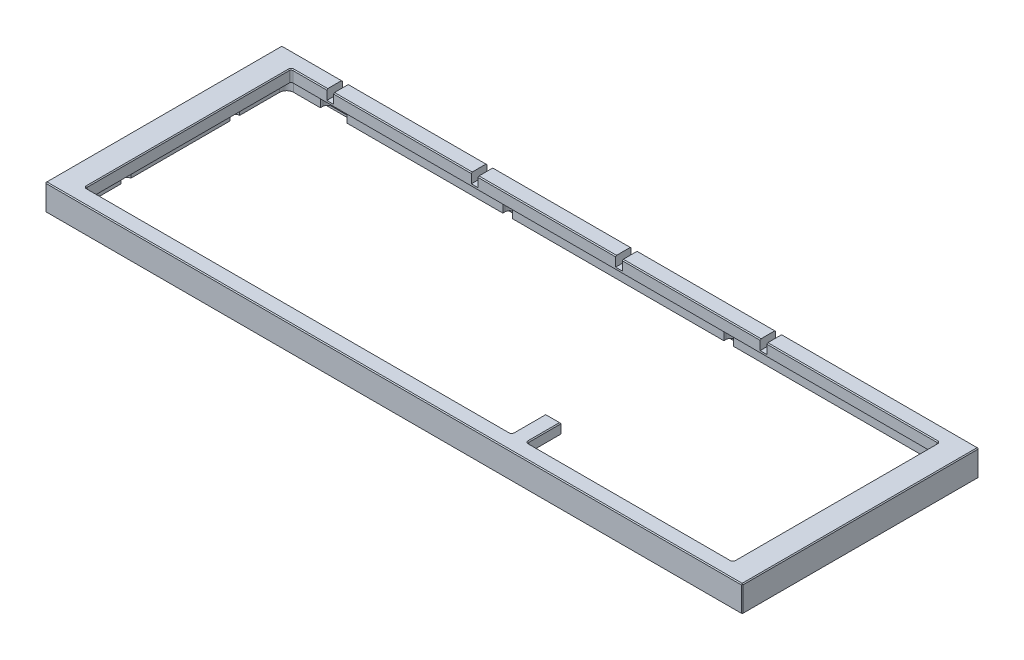
SolidWorks part; units mm, degrees
material "6061-T6 (SS)"
ref_plane "Front Plane" through (0, 0, 0) normal (0, 0, 1) x (1, 0, 0)
ref_plane "Top Plane" through (0, 0, 0) normal (0, 1, 0) x (1, 0, 0)
ref_plane "Right Plane" through (0, 0, 0) normal (1, 0, 0) x (0, 0, -1)
sketch "Sketch1" plane through (0, 0, 0) normal (0, 1, 0) x (1, 0, 0)
  line L1 (0, 0) -> (390.74, 0)
  line L2 (0, 0) -> (0, 132.7)
  line L3 (0, 132.7) -> (390.74, 132.7)
  line L4 (390.74, 0) -> (390.74, 132.7)
  line L5 (13.92, 124) -> (376.82, 124)
  line L6 (13.92, 124) -> (13.92, 8.7)
  line L7 (13.92, 8.7) -> (376.82, 8.7)
  line L8 (376.82, 124) -> (376.82, 8.7)
  point P9 (195.37, 124)
  point P10 (195.37, 132.7)
  point P11 (13.92, 66.35)
  point P12 (0, 66.35)
  dimension "D1" = 362.9
  dimension "D2" = 115.3
  dimension "D3" = 8.7
  dimension "D4" = 13.92
extrude "Main Body" add sketch "Sketch1" along normal blind 14.8
sketch "Sketch2" plane through (0, 0, 0) normal (0, -1, 0) x (1, 0, 0)
  line L0 (390.74, -132.7) -> (0, -132.7) construction
  line L1 (388.74, -130.7) -> (2, -130.7)
  line L2 (388.74, -130.7) -> (388.74, -2)
  line L3 (388.74, -2) -> (2, -2)
  line L4 (2, -130.7) -> (2, -2)
  line L5 (390.74, 0) -> (390.74, -132.7) construction
  point P4 (195.37, -130.7)
  point P7 (195.37, -132.7)
  point P8 (388.74, -66.35)
  point P11 (390.74, -66.35)
  dimension "D1" = 2
  dimension "D2" = 2
extrude "Alignment Guide" cut sketch "Sketch2" against normal blind 2 contours L2 L1 L4 L3
sketch "Sketch3" plane through (0, 14.8, 0) normal (0, 1, 0) x (1, 0, 0)
  line L0 (13.92, 8.7) -> (376.82, 8.7) construction
  line L1 (252.82, 27.8) -> (261.52, 27.8)
  line L2 (252.82, 27.8) -> (252.82, 8.7)
  line L3 (252.82, 8.7) -> (261.52, 8.7)
  line L4 (261.52, 27.8) -> (261.52, 8.7)
  line L5 (376.82, 8.7) -> (376.82, 124) construction
  line L6 (376.82, 124) -> (13.92, 124) construction
  line L7 (33.92, 124) -> (37.72, 124)
  line L8 (33.92, 124) -> (33.92, 104.9)
  line L9 (33.92, 104.9) -> (37.72, 104.9)
  line L10 (37.72, 124) -> (37.72, 104.9)
  line L11 (13.92, 124) -> (13.92, 8.7) construction
  line L12 (114.92, 124) -> (118.72, 124)
  line L13 (114.92, 124) -> (114.92, 104.9)
  line L14 (114.92, 104.9) -> (118.72, 104.9)
  line L15 (118.72, 124) -> (118.72, 104.9)
  line L16 (195.82, 124) -> (199.62, 124)
  line L17 (195.82, 124) -> (195.82, 104.9)
  line L18 (195.82, 104.9) -> (199.62, 104.9)
  line L19 (199.62, 124) -> (199.62, 104.9)
  line L20 (276.82, 124) -> (280.62, 124)
  line L21 (276.82, 124) -> (276.82, 104.9)
  line L22 (276.82, 104.9) -> (280.62, 104.9)
  line L23 (280.62, 124) -> (280.62, 104.9)
  point P8 (257.17, 8.7)
  dimension "D1" = 115.3
  dimension "D2" = 124
  dimension "D3" = 19.1
  dimension "D4" = 3.8
  dimension "D5" = 19.1
  dimension "D6" = 77.2
  dimension "D7" = 77.1
  dimension "D8" = 77.2
  dimension "D9" = 20
extrude "Blockers" add sketch "Sketch3" against normal blind 5.5
fillet "Fillet5" radius 1 6 edges at (13.92, 8.4, -124) (13.92, 8.4, -8.7) (252.82, 12.05, -8.7) (261.52, 12.05, -8.7) (376.82, 8.4, -8.7) (376.82, 8.4, -124)
sketch "Sketch4" plane through (0, 2, 0) normal (0, -1, 0) x (1, 0, 0)
  line L0 (0, 0) -> (390.74, 0) construction
  line L1 (381.27, -125.9) -> (9.47, -125.9)
  line L2 (381.27, -125.9) -> (381.27, -6.8)
  line L3 (381.27, -6.8) -> (9.47, -6.8)
  line L4 (9.47, -125.9) -> (9.47, -6.8)
  line L5 (390.74, 0) -> (390.74, -132.7) construction
  point P4 (195.37, -6.8)
  point P7 (195.37, 0)
  point P8 (381.27, -66.35)
  point P11 (390.74, -66.35)
  dimension "D1" = 119.1
  dimension "D2" = 371.8
extrude "PCB Cutout" cut sketch "Sketch4" against normal offset from surface (6.3 mm away) 6.5 up to face at (195.37, 14.8, -66.35)
fillet "Fillet4" radius 4 8 edges at (9.47, 5.15, -6.8) (9.47, 5.15, -125.9) (381.27, 5.15, -125.9) (381.27, 5.15, -6.8) (2, 1, -130.7) (2, 1, -2) (388.74, 1, -2) (388.74, 1, -130.7)
sketch "Sketch6" plane through (0, 2, 0) normal (0, -1, 0) x (1, 0, 0)
  line L0 (381.27, -10.8) -> (381.27, -121.9) construction
  line L1 (254.59, -127.1) -> (260.09, -127.1)
  line L2 (254.59, -127.1) -> (254.59, -125.9)
  line L3 (254.59, -125.9) -> (260.09, -125.9)
  line L4 (260.09, -127.1) -> (260.09, -125.9)
  line L5 (13.47, -125.9) -> (377.27, -125.9) construction
  line L11 (377.27, -6.8) -> (13.47, -6.8) construction
  line L16 (260.09, -6.8) -> (254.59, -6.8)
  line L17 (260.09, -6.8) -> (260.09, -4.8)
  line L18 (260.09, -4.8) -> (254.59, -4.8)
  line L19 (254.59, -6.8) -> (254.59, -4.8)
  line L21 (0, 0) -> (390.74, 0) construction
  line L24 (390.74, -66.35) -> (195.37, -66.35) construction
  line L25 (390.74, 0) -> (390.74, -132.7) construction
  line L26 (328.6755, -66.35) -> (328.6755, -130.7) construction
  line L27 (384.74, -130.7) -> (6, -130.7) construction
  line L28 (328.6755, -66.35) -> (328.6755, -8.7) construction
  line L29 (375.82, -8.7) -> (14.92, -8.7) construction
  line L55 (390.74, -132.7) -> (0, -132.7) construction
  line L56 (195.37, -132.7) -> (195.37, 0) construction
  line L57 (136.15, -6.8) -> (136.15, -4.8)
  line L58 (130.65, -4.8) -> (136.15, -4.8)
  line L59 (130.65, -6.8) -> (130.65, -4.8)
  line L60 (130.65, -6.8) -> (136.15, -6.8)
  line L61 (130.65, -127.1) -> (130.65, -125.9)
  line L62 (136.15, -125.9) -> (130.65, -125.9)
  line L63 (136.15, -127.1) -> (136.15, -125.9)
  line L64 (136.15, -127.1) -> (130.65, -127.1)
  circle A0 centre (381.07, -96.85) radius 2.75
  circle A1 centre (381.07, -35.85) radius 2.75
  circle A2 centre (257.34, -4.8) radius 2.75
  circle A3 centre (257.34, -127.1) radius 2.75
  circle A8 centre (133.4, -4.8) radius 2.75
  circle A9 centre (9.67, -35.85) radius 2.75
  circle A10 centre (9.67, -96.85) radius 2.75
  circle A11 centre (133.4, -127.1) radius 2.75
  point P25 (195.37, -66.35)
  point P32 (257.34, -125.9)
  point P33 (257.34, -6.8)
  line M17 (13.47, -6.8) -> (377.27, -6.8)
  line M18 (381.27, -10.8) -> (381.27, -121.9)
  line M19 (377.27, -125.9) -> (13.47, -125.9)
  line M20 (9.47, -121.9) -> (9.47, -10.8)
  dimension "D4" = 5.5
  dimension "D5" = 133.4
  dimension "D1" = 30.5
  dimension "D2" = 4.8
  dimension "D3" = 30.5
  dimension "D6" = 0.2
  dimension "D7" = 5.6
extrude "PlateTabs" cut sketch "Sketch6" against normal up to surface (6.3 mm away) contours A0 M18 | A1 M18 | A2 L19 M17 | L16 A2 L18 | A2 L17 M17 | L18 A2 | L1 A3 | L1 A3 L3 | A3 L2 M19 | A11 L64 | A11 L64 L62 | A10 M20 | A9 M20 | A8 L58 | A8 L60 L58 | A3 L4 M19 | A8 L59 M17 | L57 A8 M17 | A11 L63 M19 | L61 A11 M19 | A11 | L59 L58 L57 L60 | A3 region at (257.34, 2, -126.5102) region at (136.0681, 2, -126.1969) region at (257.34, 2, -128.2671) region at (254.6719, 2, -126.1969) region at (260.0081, 2, -126.1969) region at (133.4, 2, -126.5102) region at (133.4, 2, -128.2671) region at (130.7319, 2, -126.1969) region at (135.9001, 2, -6.317) region at (259.8401, 2, -6.317) region at (257.34, 2, -5.7445) region at (257.34, 2, -3.6329) region at (254.8399, 2, -6.317) region at (133.4, 2, -5.7445) region at (133.4, 2, -3.6329) region at (130.8999, 2, -6.317) region at (382.3459, 2, -96.85) region at (382.3459, 2, -35.85) region at (8.3941, 2, -96.85) region at (8.3941, 2, -35.85) up to face at (195.37, 8.3, -66.35)
sketch "Sketch9" plane through (0, 0, -132.7) normal (0, 0, -1) x (-1, 0, 0)
  line L1 (-40.9, 3) -> (-30.9, 3)
  line L2 (-40.9, 3) -> (-40.9, 6.8)
  line L3 (-40.9, 6.8) -> (-30.9, 6.8)
  line L4 (-30.9, 3) -> (-30.9, 6.8)
  line L7 (0, 14.8) -> (0, 0) construction
  line L8 (-390.74, 0) -> (0, 0) construction
  point P4 (-30.9, 4.9)
  point P6 (-35.9, 6.8)
  dimension "D1" = 4.9
  dimension "D2" = 3.8
  dimension "D3" = 10
  dimension "D4" = 35.9
extrude "USB Cutout" cut sketch "Sketch9" against normal up to surface (8.7 mm away) up to face at (164.89, 11.95, -124)
sketch "Sketch10" plane through (0, 0, -132.7) normal (0, 0, -1) x (-1, 0, 0)
  line L0 (-30.9, 6.8) -> (-40.9, 6.8) construction
  line L1 (-42.9, 8.8) -> (-28.9, 8.8)
  line L2 (-42.9, 8.8) -> (-42.9, 1)
  line L3 (-42.9, 1) -> (-28.9, 1)
  line L4 (-28.9, 8.8) -> (-28.9, 1)
  line L5 (-40.9, 6.8) -> (-40.9, 3) construction
  point P4 (-35.9, 8.8)
  point P7 (-35.9, 6.8)
  point P10 (-40.9, 4.9)
  point P11 (-42.9, 4.9)
  dimension "D1" = 2
  dimension "D2" = 2
extrude "USB Outline" cut sketch "Sketch10" against normal blind 1
sketch "Sketch11" plane through (0, 0, -125.9) normal (0, 0, 1) x (1, 0, 0)
  line L1 (43.4, 2) -> (28.4, 2)
  line L2 (43.4, 2) -> (43.4, 6.8)
  line L3 (43.4, 6.8) -> (28.4, 6.8)
  line L4 (28.4, 2) -> (28.4, 6.8)
  line L5 (30.9, 6.8) -> (40.9, 6.8) construction
  line L6 (40.9, 3) -> (30.9, 3) construction
  line L7 (13.47, 2) -> (130.65, 2) construction
  point P8 (35.9, 2)
  point P11 (35.9, 3)
  dimension "D1" = 15
extrude "PCB Clearance" cut sketch "Sketch11" against normal blind 3.9
fillet "Fillet6" radius 1.5 8 edges at (40.9, 6.8, -130.75) (30.9, 6.8, -130.75) (40.9, 3, -130.75) (42.9, 1, -132.2) (42.9, 8.8, -132.2) (28.9, 8.8, -132.2) (30.9, 3, -130.75) (28.9, 1, -132.2)
fillet "Fillet7" radius 2.5 2 edges at (28.4, 4.4, -129.8) (43.4, 4.4, -129.8)
sketch "Sketch12" plane through (0, 8.3, 0) normal (0, -1, 0) x (1, 0, 0)
  line L0 (195.37, -132.7) -> (195.37, 0) construction
  line L1 (390.74, -132.7) -> (0, -132.7) construction
  line L2 (14.92, -124) -> (375.82, -124) construction
  line L3 (0, 0) -> (390.74, 0) construction
  line L4 (390.74, 0) -> (390.74, -132.7) construction
  line L8 (376.82, -123) -> (376.82, -9.7) construction
  line L9 (375.82, -8.7) -> (14.92, -8.7) construction
  arc A0 (381.27, -38.5927) -> (381.27, -33.1073) centre (381.07, -35.85) ccw construction
  arc A1 (381.27, -99.5927) -> (381.27, -94.1073) centre (381.07, -96.85) ccw construction
  point P0 (257.34, -127.1)
  point P1 (381.42, -96.85)
  point P2 (381.42, -35.85)
  point P3 (257.34, -4.8)
  point P8 (133.4, -4.8)
  point P10 (9.32, -35.85)
  point P14 (9.32, -96.85)
  point P16 (133.4, -127.1)
  point P34 (383.82, -35.85)
  point P39 (383.82, -96.85)
  dimension "D1" = 3.1
  dimension "D2" = 3.9
  dimension "D3" = 4.6
  dimension "D4" = 133.4
sketch "Sketch14" plane through (0, 2, 0) normal (0, -1, 0) x (1, 0, 0)
  line L0 (195.37, -132.7) -> (195.37, 0) construction
  line L1 (390.74, -132.7) -> (0, -132.7) construction
  line L2 (0, 0) -> (390.74, 0) construction
  line L5 (195.37, -66.35) -> (390.74, -66.35) construction
  line L6 (390.74, 0) -> (390.74, -132.7) construction
  line L7 (388.74, -126.7) -> (388.74, -6) construction
  line L8 (384.74, -130.7) -> (6, -130.7) construction
  line L9 (384.74, -2) -> (6, -2) construction
  point P8 (385.04, -111.35)
  point P9 (385.04, -66.35)
  point P10 (385.04, -21.35)
  point P11 (280.74, -4.4)
  point P20 (280.74, -128.3)
  point P22 (110, -4.4)
  point P28 (110, -128.3)
  point P29 (5.7, -21.35)
  point P30 (5.7, -66.35)
  point P31 (5.7, -111.35)
  dimension "D1" = 2.4
  dimension "D2" = 2.4
  dimension "D3" = 110
  dimension "D4" = 45
  dimension "D5" = 45
  dimension "D6" = 3.7
chamfer "Chamfer1" distance 0.5 34 edges at (14.2129, 14.8, -8.9929) (133.37, 14.8, -8.7) (252.5271, 14.8, -8.9929) (252.82, 14.8, -18.75) (257.17, 14.8, -27.8) (261.52, 14.8, -18.75) (261.8129, 14.8, -8.9929) (319.17, 14.8, -8.7) (376.5271, 14.8, -8.9929) (376.82, 14.8, -66.35) (376.5271, 14.8, -123.7071) (328.22, 14.8, -124) (280.62, 14.8, -114.45) (278.72, 14.8, -104.9) (276.82, 14.8, -114.45) (199.62, 14.8, -114.45) (197.72, 14.8, -104.9) (195.82, 14.8, -114.45) (118.72, 14.8, -114.45) (116.82, 14.8, -104.9) (114.92, 14.8, -114.45) (37.72, 14.8, -114.45) (35.82, 14.8, -104.9) (33.92, 14.8, -114.45) (24.42, 14.8, -124) (14.2129, 14.8, -123.7071) (13.92, 14.8, -66.35) (195.37, 14.8, -132.7) (390.74, 14.8, -66.35) (195.37, 14.8, 0) (0, 14.8, -66.35) (238.22, 14.8, -124) (157.27, 14.8, -124) (76.32, 14.8, -124)
chamfer "Chamfer2" distance 0.5 8 edges at (0, 7.15, -132.7) (195.37, 0, -132.7) (390.74, 7.15, -132.7) (390.74, 0, -66.35) (390.74, 7.15, 0) (0, 7.15, 0) (195.37, 0, 0) (0, 0, -66.35)
hole_wizard "M3x0.5 Tapped Hole1" positions "3DSketch1" profile "Sketch29" tap size "M3x0.5" standard "ANSI Metric"
sketch3d "3DSketch1"
  point P0 (385.04, 2, -111.35)
  point P3 (385.04, 2, -21.35)
  point P6 (280.74, 2, -4.4)
  point P9 (110, 2, -4.4)
  point P12 (5.7, 2, -21.35)
  point P15 (5.7, 2, -66.35)
  point P18 (5.7, 2, -111.35)
  point P21 (110, 2, -128.3)
  point P24 (280.74, 2, -128.3)
  point P28 (385.04, 2, -66.35)
sketch "Sketch29" plane through (385.04, 2, -111.35) normal (1, 0, 0) x (0, 0, -1)
  line L0 (0, 0) -> (0, 4.7511)
  line L1 (0, 4.7511) -> (1.25, 4)
  line L2 (1.25, 4) -> (1.25, 0)
  line L5 (1.25, 0) -> (0, 0)
  line L10 (0, 4.7511) -> (-1.25, 4) construction
  line L11 (0, -6.35) -> (0, 107.95) construction
  dimension "Tap Drill Dia." = 2.5
  dimension "Tap Drill Depth" = 4
  dimension "Drill Angle" = 118
cosmetic thread "Hole Thread1" parameters "D1"=4, "D2"=3
cosmetic thread "Hole Thread2" parameters "D1"=4, "D2"=3
cosmetic thread "Hole Thread3" parameters "D1"=4, "D2"=3
cosmetic thread "Hole Thread4" parameters "D1"=4, "D2"=3
cosmetic thread "Hole Thread5" parameters "D1"=4, "D2"=3
cosmetic thread "Hole Thread6" parameters "D1"=4, "D2"=3
cosmetic thread "Hole Thread7" parameters "D1"=4, "D2"=3
cosmetic thread "Hole Thread8" parameters "D1"=4, "D2"=3
cosmetic thread "Hole Thread9" parameters "D1"=4, "D2"=3
cosmetic thread "Hole Thread18" parameters "D1"=4, "D2"=3
hole_wizard "M2x0.4 Tapped Hole4" positions "3DSketch3" profile "Sketch31" tap size "M2x0.4" standard "ANSI Metric"
sketch3d "3DSketch3"
  line L0 (381.07, 8.3, -96.85) -> (381.07, 2, -96.85) construction
  line L1 (381.07, 8.3, -35.85) -> (381.07, 2, -35.85) construction
  line L2 (9.67, 8.3, -35.85) -> (9.67, 2, -35.85) construction
  line L3 (9.67, 8.3, -96.85) -> (9.67, 2, -96.85) construction
  point P0 (381.07, 8.3, -96.85)
  point P5 (381.07, 8.3, -35.85)
  point P9 (257.34, 8.3, -4.8)
  point P12 (133.4, 8.3, -4.8)
  point P15 (9.67, 8.3, -35.85)
  point P19 (9.67, 8.3, -96.85)
  point P23 (133.4, 8.3, -127.1)
  point P26 (257.34, 8.3, -127.1)
sketch "Sketch31" plane through (381.07, 8.3, -96.85) normal (1, 0, 0) x (0, 0, -1)
  line L0 (0, 0) -> (0, 4.4807)
  line L1 (0, 4.4807) -> (0.8, 4)
  line L2 (0.8, 4) -> (0.8, 0)
  line L5 (0.8, 0) -> (0, 0)
  line L10 (0, 4.4807) -> (-0.8, 4) construction
  line L11 (0, -6.35) -> (0, 107.95) construction
  dimension "Tap Drill Dia." = 1.6
  dimension "Tap Drill Depth" = 4
  dimension "Drill Angle" = 118
cosmetic thread "Hole Thread19" parameters "D1"=4, "D2"=2
cosmetic thread "Hole Thread20" parameters "D1"=4, "D2"=2
cosmetic thread "Hole Thread21" parameters "D1"=4, "D2"=2
cosmetic thread "Hole Thread22" parameters "D1"=4, "D2"=2
cosmetic thread "Hole Thread23" parameters "D1"=4, "D2"=2
cosmetic thread "Hole Thread24" parameters "D1"=4, "D2"=2
cosmetic thread "Hole Thread25" parameters "D1"=4, "D2"=2
cosmetic thread "Hole Thread26" parameters "D1"=4, "D2"=2
sketch "Sketch27" [suppressed] plane through (0, 14.8, 0) normal (0, 1, 0) x (1, 0, 0)
  line L0 (0, 0.5) -> (0, 132.2) construction
  line L1 (0, 129.7) -> (390.74, 129.7)
  line L2 (0, 129.7) -> (0, 127.2)
  line L3 (0, 127.2) -> (390.74, 127.2)
  line L4 (390.74, 129.7) -> (390.74, 127.2)
  line L5 (390.74, 132.2) -> (390.74, 0.5) construction
  line L8 (0.5, 132.7) -> (390.24, 132.7) construction
  dimension "D1" = 2.5
  dimension "D2" = 3
extrude "Cut-Extrude11" [suppressed] cut sketch "Sketch27" against normal blind 1
sketch "Sketch28" [suppressed] plane through (0, 13.8, 0) normal (0, 1, 0) x (1, 0, 0)
  line L1 (0, 129.7) -> (1, 129.7)
  line L2 (0, 129.7) -> (0, 127.2)
  line L3 (0, 127.2) -> (1, 127.2)
  line L4 (1, 129.7) -> (1, 127.2)
  line L5 (389.74, 129.7) -> (390.74, 129.7)
  line L6 (389.74, 129.7) -> (389.74, 127.2)
  line L7 (389.74, 127.2) -> (390.74, 127.2)
  line L8 (390.74, 129.7) -> (390.74, 127.2)
  line L9 (390.74, 129.7) -> (0, 129.7) construction
  line L10 (0, 127.2) -> (390.74, 127.2) construction
  dimension "D1" = 1
  dimension "D2" = 1
extrude "Cut-Extrude12" [suppressed] cut sketch "Sketch28" against normal through all
sketch "Sketch21" [suppressed] plane through (0, 14.8, 0) normal (0, 1, 0) x (1, 0, 0)
  line L0 (0.5, 132.7) -> (390.24, 132.7) construction
  line L1 (382.53, 132.7) -> (385.03, 132.7)
  line L2 (382.53, 132.7) -> (382.53, 72.7)
  line L3 (382.53, 72.7) -> (385.03, 72.7)
  line L4 (385.03, 132.7) -> (385.03, 72.7)
  line L5 (390.74, 132.2) -> (390.74, 129.7) construction
  line L6 (390.74, 129.1) -> (294.74, 129.1)
  line L7 (390.74, 129.1) -> (390.74, 127.6)
  line L8 (390.74, 127.6) -> (294.74, 127.6)
  line L9 (294.74, 129.1) -> (294.74, 127.6)
  line L10 (362.9081, 132.2) -> (362.9081, 124.5) construction
  line L11 (390.24, 132.2) -> (0.5, 132.2) construction
  line L12 (281.62, 124.5) -> (375.82, 124.5) construction
  line L13 (365.5702, 129.1) -> (365.5702, 127.6) construction
  line L14 (377.32, 119.5259) -> (390.24, 119.5259) construction
  line L15 (377.32, 123) -> (377.32, 9.7) construction
  line L16 (390.24, 0.5) -> (390.24, 127.2) construction
  line L17 (382.53, 116.0504) -> (385.03, 116.0504) construction
  point P28 (383.78, 116.0504)
  point P29 (383.78, 119.5259)
  point P30 (365.5702, 128.35)
  point P31 (362.9081, 128.35)
  dimension "D1" = 2.5
  dimension "D2" = 1.5
  dimension "D3" = 60
  dimension "D4" = 96
extrude "Cut-Extrude5" [suppressed] cut sketch "Sketch21" against normal blind 1 contours L4 L3 L2 L1 | L8 L9 L6 L7
sketch "Sketch23" [suppressed] plane through (390.74, 0, 0) normal (1, 0, 0) x (0, 0, -1)
  line L0 (129.1, 13.8) -> (129.1, 14.3) construction
  line L1 (127.6, 13.8) -> (129.1, 13.8)
  line L2 (127.6, 13.8) -> (127.6, 0)
  line L3 (127.6, 0) -> (129.1, 0)
  line L4 (129.1, 13.8) -> (129.1, 0)
extrude "Cut-Extrude6" [suppressed] cut sketch "Sketch23" against normal blind 1
sketch "Sketch20" plane through (0, 14.8, 0) normal (0, 1, 0) x (1, 0, 0)
  line L0 (0, 0.5) -> (0, 132.2) construction
  line L1 (0, 129.1) -> (390.74, 129.1)
  line L2 (0, 129.1) -> (0, 127.6)
  line L3 (0, 127.6) -> (390.74, 127.6)
  line L4 (390.74, 129.1) -> (390.74, 127.6)
  line L5 (390.74, 132.2) -> (390.74, 0.5) construction
  line L6 (0.5, 132.7) -> (390.24, 132.7) construction
  line L7 (381.7523, 132.7) -> (384.2523, 132.7)
  line L8 (381.7523, 132.7) -> (381.7523, 0)
  line L9 (381.7523, 0) -> (384.2523, 0)
  line L10 (384.2523, 132.7) -> (384.2523, 0)
  line L11 (390.24, 0) -> (0.5, 0) construction
  line L12 (376.82, 111.1489) -> (390.74, 111.1489) construction
  line L13 (376.82, 9.7) -> (376.82, 123) construction
  line L14 (381.7523, 114.604) -> (384.2523, 114.604) construction
  line L15 (369.2566, 124.5) -> (369.2566, 132.2) construction
  line L16 (280.12, 124.5) -> (375.82, 124.5) construction
  line L17 (390.24, 132.2) -> (0.5, 132.2) construction
  line L18 (371.0168, 127.6) -> (371.0168, 129.1) construction
  point P30 (371.0168, 128.35)
  point P31 (369.2566, 128.35)
  line M47 (390.24, 0.5) -> (390.24, 132.2)
  line M48 (390.24, 132.2) -> (0.5, 132.2)
  line M49 (0.5, 132.2) -> (0.5, 0.5)
  line M50 (0.5, 0.5) -> (390.24, 0.5)
  dimension "D1" = 2.5
  dimension "D2" = 1.5
extrude "Cut-Extrude4" [suppressed] cut sketch "Sketch20" against normal blind 1 contours L10 L3 L8 M50 | L10 L1 L8 L3 | L8 L1 L3 M49 | L1 L10 L3 M47 | L10 L8 L1 M48 | L4 L1 L3 M47 | L10 L7 L8 M48 | L10 L8 L9 M50 | L2 L3 L1 M49
sketch "Sketch19" plane through (0, 14.8, 0) normal (0, 1, 0) x (1, 0, 0)
  line L0 (0.5, 132.7) -> (390.24, 132.7) construction
  line L1 (5.46, 132.7) -> (8.46, 132.7)
  line L2 (5.46, 132.7) -> (5.46, 0)
  line L3 (5.46, 0) -> (8.46, 0)
  line L4 (8.46, 132.7) -> (8.46, 0)
  line L7 (382.28, 132.7) -> (385.28, 132.7)
  line L8 (382.28, 132.7) -> (382.28, 0)
  line L9 (382.28, 0) -> (385.28, 0)
  line L10 (385.28, 132.7) -> (385.28, 0)
  line L11 (390.24, 0) -> (0.5, 0) construction
  line L12 (377.32, 110.209) -> (390.24, 110.209) construction
  line L13 (377.32, 123) -> (377.32, 9.7) construction
  line L14 (390.24, 0.5) -> (390.24, 132.2) construction
  line L15 (382.28, 106.8719) -> (385.28, 106.8719) construction
  line L16 (0.5, 106.8719) -> (13.42, 106.8719) construction
  line L17 (0.5, 132.2) -> (0.5, 0.5) construction
  line L18 (13.42, 9.7) -> (13.42, 123) construction
  line L19 (5.46, 102.7297) -> (8.46, 102.7297) construction
  point P12 (383.78, 106.8719)
  point P14 (383.78, 110.209)
  point P30 (6.96, 102.7297)
  point P31 (6.96, 106.8719)
  dimension "D1" = 3
  dimension "D2" = 3
extrude "Cut-Extrude3" [suppressed] cut sketch "Sketch19" against normal blind 1
sketch "Sketch17" plane through (0, 14.8, 0) normal (0, 1, 0) x (1, 0, 0)
  line L0 (390.24, 0.5) -> (390.24, 132.2) construction
  line L1 (5.71, 129.6) -> (385.03, 129.6)
  line L2 (5.71, 129.6) -> (5.71, 3.1)
  line L3 (5.71, 3.1) -> (385.03, 3.1)
  line L4 (385.03, 129.6) -> (385.03, 3.1)
  line L5 (8.21, 127.1) -> (382.53, 127.1)
  line L6 (8.21, 127.1) -> (8.21, 5.6)
  line L7 (8.21, 5.6) -> (382.53, 5.6)
  line L8 (382.53, 127.1) -> (382.53, 5.6)
  line L9 (390.24, 132.2) -> (0.5, 132.2) construction
  line L10 (21.2533, 132.2) -> (21.2533, 124.5) construction
  line L11 (14.92, 124.5) -> (34.42, 124.5) construction
  line L12 (25.2757, 129.6) -> (25.2757, 127.1) construction
  line L13 (0.5, 116.1326) -> (13.42, 116.1326) construction
  line L14 (0.5, 132.2) -> (0.5, 0.5) construction
  line L15 (13.42, 9.7) -> (13.42, 123) construction
  line L16 (5.71, 120.1548) -> (8.21, 120.1548) construction
  point P8 (382.53, 66.35)
  point P9 (385.03, 66.35)
  point P12 (390.24, 66.35)
  point P13 (195.37, 129.6)
  point P14 (195.37, 127.1)
  point P17 (195.37, 132.2)
  point P24 (25.2757, 128.35)
  point P25 (21.2533, 128.35)
  point P34 (6.96, 116.1326)
  point P35 (6.96, 120.1548)
  dimension "D1" = 2.5
  dimension "D2" = 2.5
extrude "Cut-Extrude1" [suppressed] cut sketch "Sketch17" against normal blind 1
sketch "Sketch32" plane through (0, 14.8, 0) normal (0, 1, 0) x (1, 0, 0)
  line L0 (0.5, 132.7) -> (390.24, 132.7) construction
  line L1 (33.92, 132.7) -> (37.72, 132.7)
  line L2 (33.92, 132.7) -> (33.92, 104.9)
  line L3 (33.92, 104.9) -> (37.72, 104.9)
  line L4 (37.72, 132.7) -> (37.72, 104.9)
  line L5 (33.92, 104.9) -> (33.92, 124) construction
  line L6 (114.92, 132.7) -> (118.72, 132.7)
  line L7 (114.92, 132.7) -> (114.92, 104.9)
  line L8 (114.92, 104.9) -> (118.72, 104.9)
  line L9 (118.72, 132.7) -> (118.72, 104.9)
  line L10 (195.82, 132.7) -> (199.62, 132.7)
  line L11 (195.82, 132.7) -> (195.82, 104.9)
  line L12 (195.82, 104.9) -> (199.62, 104.9)
  line L13 (199.62, 132.7) -> (199.62, 104.9)
  line L14 (276.82, 132.7) -> (280.62, 132.7)
  line L15 (276.82, 132.7) -> (276.82, 104.9)
  line L16 (276.82, 104.9) -> (280.62, 104.9)
  line L17 (280.62, 132.7) -> (280.62, 104.9)
  line L18 (114.92, 104.9) -> (114.92, 124) construction
  line L19 (195.82, 104.9) -> (195.82, 124) construction
  line L20 (276.82, 104.9) -> (276.82, 124) construction
extrude "Cut-Extrude13" cut sketch "Sketch32" against normal blind 5.5
